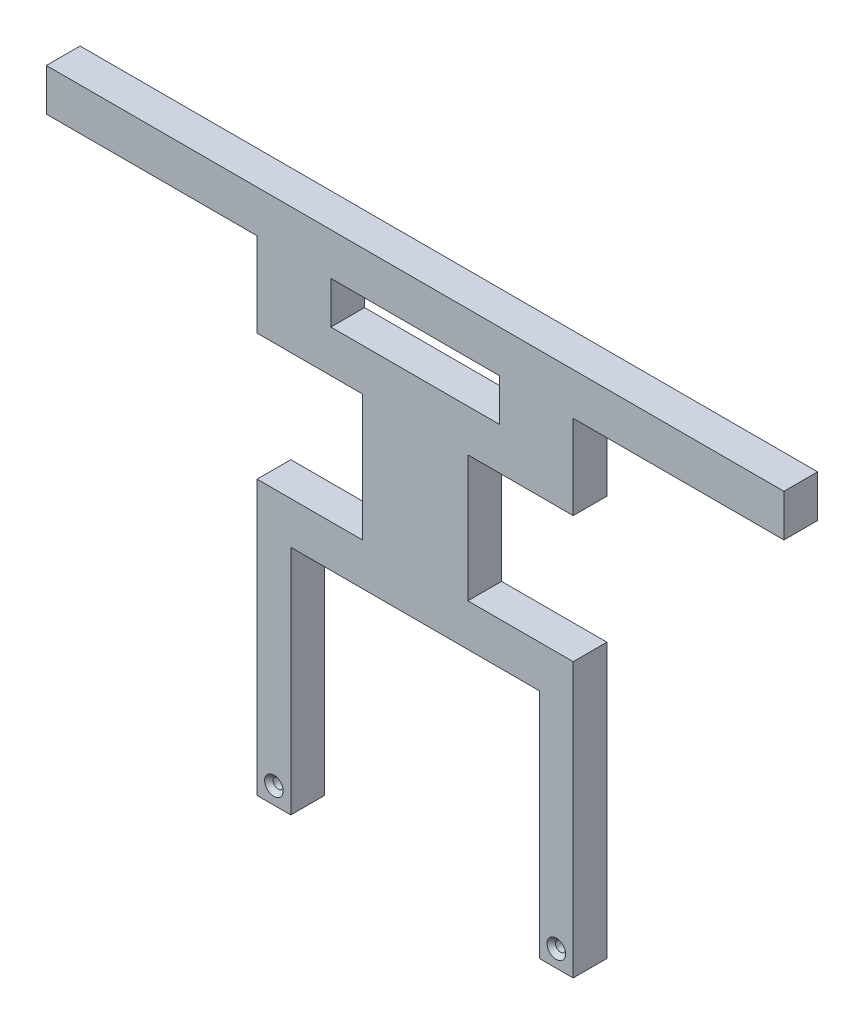
SolidWorks part; units mm, degrees
ref_plane "Plan de face" through (0, 0, 0) normal (0, 0, 1) x (1, 0, 0)
ref_plane "Plan de dessus" through (0, 0, 0) normal (0, 1, 0) x (1, 0, 0)
ref_plane "Plan de droite" through (0, 0, 0) normal (1, 0, 0) x (0, 0, -1)
sketch "Esquisse1" plane through (0, 0, 0) normal (0, 0, 1) x (1, 0, 0)
  line L20 (0, 0) -> (0, 65)
  line L21 (0, 65) -> (25, 65)
  line L22 (25, 65) -> (25, 95)
  line L23 (25, 95) -> (0, 95)
  line L24 (0, 95) -> (0, 115)
  line L25 (0, 115) -> (-50, 115)
  line L26 (-50, 115) -> (-50, 125)
  line L27 (-50, 125) -> (37.5, 125)
  line L28 (37.5, 125) -> (37.5, 115)
  line L29 (37.5, 115) -> (17.5, 115)
  line L30 (17.5, 115) -> (17.5, 105)
  line L31 (17.5, 105) -> (37.5, 105)
  line L32 (37.5, 105) -> (37.5, 55)
  line L33 (37.5, 55) -> (8, 55)
  line L34 (8, 55) -> (8, 0)
  line L35 (8, 0) -> (0, 0)
  point P13 (0, 0)
  point P18 (27.6349, 7.6542)
  point P19 (0, 0)
  point P20 (0, 0)
  point P21 (0, 0)
  point P22 (0, 0)
  point P24 (28.3562, -5.3297)
  point P25 (28.7169, 0)
  dimension "D1" = 65
  dimension "D2" = 8
  dimension "D3" = 55
  dimension "D4" = 25
  dimension "D5" = 30
  dimension "D6" = 20
  dimension "D7" = 50
  dimension "D8" = 10
  dimension "D9" = 29.5
  dimension "D10" = 10
  dimension "20" = 20
  dimension "D11" = 20
  dimension "D12" = 50
extrude "Boss.-Extru.1" add sketch "Esquisse1" along normal blind 8
mirror "Symétrie1" about plane through (37.5, 105, 8) normal (-1, 0, 0) of "Boss.-Extru.1"
sketch "Esquisse2" plane through (0, 0, 8) normal (0, 0, 1) x (1, 0, 0)
  line L0 (8, 0) -> (8, 55) construction
  line L1 (0, 0) -> (8, 0) construction
  line L2 (75, 65) -> (75, 0) construction
  line L3 (75, 0) -> (67, 0) construction
  circle A0 centre (4, 4) radius 1
  circle A1 centre (71, 4) radius 1
  dimension "D3" = 2
  dimension "D6" = 2
  dimension "D1" = 4
  dimension "D2" = 4
  dimension "D4" = 4
  dimension "D5" = 4
hole_wizard "Fraisage pour vis à tête fraisée M21" positions "Esquisse3" profile "Esquisse5" countersink size "M2" standard "ISO" end condition through all
sketch "Esquisse3" plane through (0, 0, 8) normal (0, 0, 1) x (1, 0, 0)
  point P0 (4, 4)
  point P3 (71, 4)
sketch "Esquisse5" plane through (4, 4, 8) normal (1, 0, 0) x (0, -1, 0)
  line L0 (0, 0) -> (0, 8)
  line L1 (0, 8) -> (1.2, 8)
  line L2 (1.2, 8) -> (1.2, 1)
  line L3 (1.2, 1) -> (2.2, 0)
  line L5 (2.2, 0) -> (0, 0)
  line L6 (-1.2, 1) -> (-2.2, 0) construction
  line L11 (0, -6.35) -> (0, 107.95) construction
  dimension "Diamètre du perçage jusqu'au prochain" = 2.4
  dimension "Profondeur du perçage jusqu'au prochain" = 8
  dimension "Diamètre du fraisage entrant" = 4.4
  dimension "Angle du fraisage entrant" = 90
